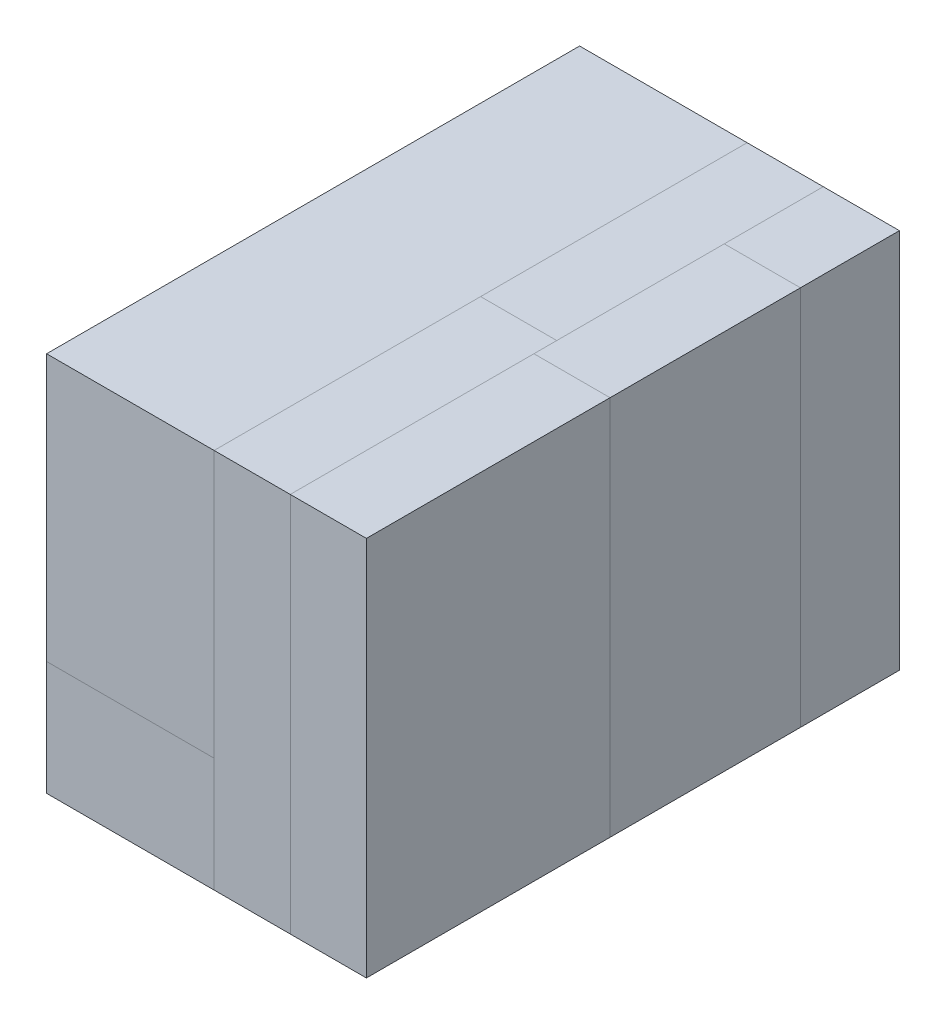
SolidWorks part; units mm, degrees
ref_plane "前视基准面" through (0, 0, 0) normal (0, 0, 1) x (1, 0, 0)
ref_plane "上视基准面" through (0, 0, 0) normal (0, 1, 0) x (1, 0, 0)
ref_plane "右视基准面" through (0, 0, 0) normal (1, 0, 0) x (0, 0, -1)
sketch "草图1" plane through (0, 0, 0) normal (0, 1, 0) x (1, 0, 0)
  line L1 (0, 0) -> (220, 0)
  line L2 (0, 0) -> (0, 700)
  line L3 (0, 700) -> (220, 700)
  line L4 (220, 0) -> (220, 700)
  dimension "D1" = 700
  dimension "D2" = 220
extrude "墙体支撑底座" add sketch "草图1" along normal blind 150
sketch "草图3" plane through (0, 150, 0) normal (0, 1, 0) x (1, 0, 0)
  line L1 (0, 0) -> (220, 0)
  line L2 (0, 0) -> (0, 700)
  line L3 (0, 700) -> (220, 700)
  line L4 (220, 0) -> (220, 700)
extrude "18寸墙体" add sketch "草图3" along normal blind 350 separate body
sketch "草图5" plane through (220, 0, 0) normal (1, 0, 0) x (0, 0, -1)
  line L1 (0, 500) -> (350, 500)
  line L2 (0, 500) -> (0, 0)
  line L3 (0, 0) -> (350, 0)
  line L4 (350, 500) -> (350, 0)
  dimension "D1" = 500
  dimension "D2" = 350
extrude "液晶挂壁1" add sketch "草图5" along normal blind 100 separate body
sketch "草图8" plane through (220, 0, 0) normal (1, 0, 0) x (0, 0, -1)
  line L0 (350, 500) -> (0, 500) construction
  line L1 (350, 0) -> (700, 0)
  line L2 (350, 0) -> (350, 500)
  line L3 (350, 500) -> (700, 500)
  line L4 (700, 0) -> (700, 500)
  dimension "D1" = 350
extrude "液晶挂壁2" add sketch "草图8" along normal blind 100 separate body
sketch "草图6" plane through (320, 0, 0) normal (1, 0, 0) x (0, 0, -1)
  line L1 (0, 500) -> (320, 500)
  line L2 (0, 500) -> (0, 0)
  line L3 (0, 0) -> (320, 0)
  line L4 (320, 500) -> (320, 0)
  dimension "D1" = 500
  dimension "D2" = 320
extrude "19寸液晶显示器" add sketch "草图6" along normal blind 100 separate body
sketch "草图9" plane through (320, 0, 0) normal (1, 0, 0) x (0, 0, -1)
  line L0 (700, 500) -> (350, 500) construction
  line L1 (320, 0) -> (570, 0)
  line L2 (320, 0) -> (320, 500)
  line L3 (320, 500) -> (570, 500)
  line L4 (570, 0) -> (570, 500)
  dimension "D1" = 250
extrude "LED灯" add sketch "草图9" along normal blind 100 separate body
sketch "草图10" plane through (320, 0, 0) normal (1, 0, 0) x (0, 0, -1)
  line L1 (570, 0) -> (700, 0)
  line L2 (570, 0) -> (570, 500)
  line L3 (570, 500) -> (700, 500)
  line L4 (700, 0) -> (700, 500)
extrude "工具存放区" add sketch "草图10" along normal blind 100 separate body
